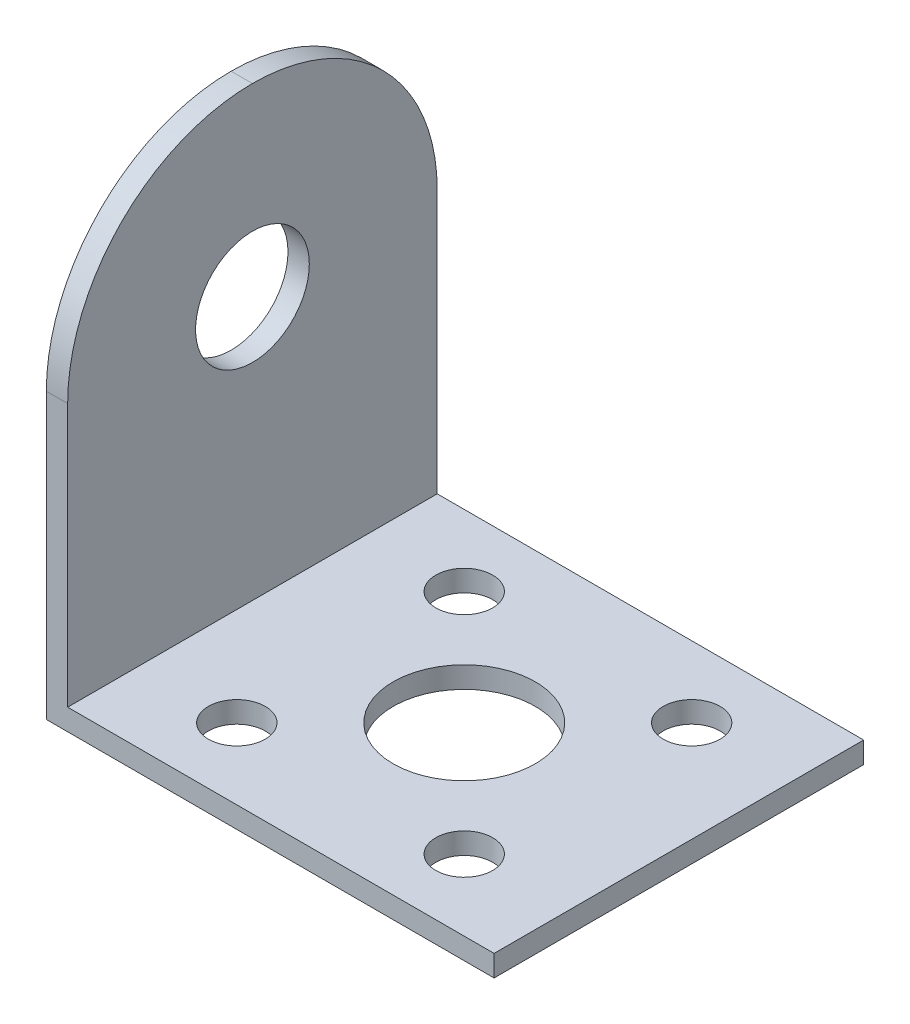
SolidWorks part; units mm, degrees
ref_plane "Front Plane" through (0, 0, 0) normal (0, 0, 1) x (1, 0, 0)
ref_plane "Top Plane" through (0, 0, 0) normal (0, 1, 0) x (1, 0, 0)
ref_plane "Right Plane" through (0, 0, 0) normal (1, 0, 0) x (0, 0, -1)
sketch "Sketch3" plane through (0, 0, 0) normal (0, 1, 0) x (1, 0, 0)
  line L1 (-15.75, 13) -> (15.75, 13)
  line L2 (-15.75, 13) -> (-15.75, -13)
  line L3 (-15.75, -13) -> (15.75, -13)
  line L4 (15.75, 13) -> (15.75, -13)
  line L5 (-15.75, 13) -> (15.75, -13) construction
  line L6 (-15.75, -13) -> (15.75, 13) construction
  point P0 (0, 0)
  dimension "D1" = 31.5
  dimension "D2" = 26
extrude "Boss-Extrude1" add sketch "Sketch3" against normal blind 1.5
sketch "Sketch4" plane through (0, 0, 0) normal (0, 1, 0) x (1, 0, 0)
  line L0 (-15.75, -13) -> (15.75, -13) construction
  line L1 (-15.75, 13) -> (-14.25, 13)
  line L2 (-15.75, 13) -> (-15.75, -13)
  line L3 (-15.75, -13) -> (-14.25, -13)
  line L4 (-14.25, 13) -> (-14.25, -13)
  dimension "D1" = 1.5
extrude "Boss-Extrude3" add sketch "Sketch4" along normal blind 31.5
fillet "Fillet3" radius 13 1 edges at (-15, 31.5, 13)
fillet "Fillet4" radius 13 1 edges at (-15, 31.5, -13)
sketch "Sketch5" plane through (-14.25, 0, 0) normal (1, 0, 0) x (0, 0, -1)
  line L0 (0, 31.5) -> (0, 18.5) construction
  circle A0 centre (0, 18.5) radius 4
  dimension "D1" = 8
extrude "Cut-Extrude1" cut sketch "Sketch5" against normal blind 31.5
ref_plane "Plane1" through (0.65, 0, 0) normal (1, 0, 0) x (0, 0, -1)
sketch "Sketch7" plane through (0, 0, 0) normal (0, 1, 0) x (1, 0, 0)
  line L0 (0.65, -14.3) -> (0.65, 14.3) construction
  line L1 (0.65, 0) -> (-7.35, 0) construction
  line L2 (-7.35, 0) -> (-7.35, -8) construction
  line L3 (-17.325, 0) -> (17.325, 0) construction
  circle A0 centre (0.65, 0) radius 5
  circle A1 centre (-7.35, -8) radius 2
  circle A2 centre (-7.35, 8) radius 2
  circle A3 centre (8.65, 8) radius 2
  circle A4 centre (8.65, -8) radius 2
  dimension "D1" = 10
  dimension "D4" = 4
  dimension "D2" = 8
  dimension "D3" = 8
extrude "Cut-Extrude2" cut sketch "Sketch7" against normal blind 10 contours A3 | A4 | A0 | A2 | A1 region at (0.65, 0, 0) region at (8.65, 0, -8) region at (8.65, 0, 8)
sketch "Sketch8" plane through (0, 0, 0) normal (0, 1, 0) x (1, 0, 0)
  line L0 (-14.25, 0) -> (15.75, 0)
  line L1 (-14.25, -13) -> (-14.25, 13) construction
  line L2 (15.75, -13) -> (15.75, 13) construction
